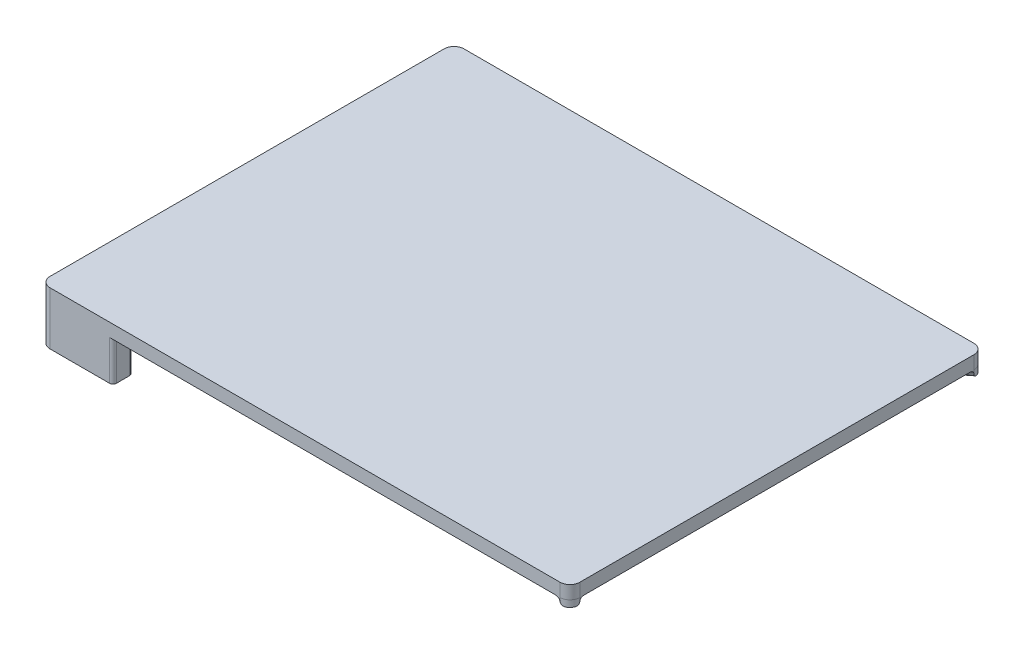
SolidWorks part; units mm, degrees
ref_plane "前视基准面" through (0, 0, 0) normal (0, 0, 1) x (1, 0, 0)
ref_plane "上视基准面" through (0, 0, 0) normal (0, 1, 0) x (1, 0, 0)
ref_plane "右视基准面" through (0, 0, 0) normal (1, 0, 0) x (0, 0, -1)
other "Configuration Table"
sketch "草图1" plane through (0, 0, 0) normal (0, 1, 0) x (1, 0, 0)
  line L1 (-42.7044, 26.7469) -> (117.2956, 26.7469)
  line L2 (-42.7044, 26.7469) -> (-42.7044, -98.2531)
  line L3 (-42.7044, -98.2531) -> (117.2956, -98.2531)
  line L4 (117.2956, 26.7469) -> (117.2956, -98.2531)
  dimension "D1" = 125
  dimension "D2" = 160
extrude "凸台-拉伸1" add sketch "草图1" along normal blind 4
sketch "草图4" plane through (0, 0, 0) normal (0, -1, 0) x (1, 0, 0)
  line L0 (-42.7044, 98.2531) -> (-20.7044, 98.2531)
  line L1 (-42.7044, 98.2531) -> (117.2956, 98.2531) construction
  line L2 (-20.7044, 98.2531) -> (-20.7044, 92.2531)
  line L6 (-36.7044, 76.2531) -> (-42.7044, 76.2531)
  line L7 (-42.7044, -26.7469) -> (-42.7044, 98.2531) construction
  line L8 (-42.7044, 76.2531) -> (-42.7044, 98.2531)
  line L11 (-36.7044, 76.2531) -> (-36.7044, 92.2531)
  line L12 (-36.7044, 92.2531) -> (-20.7044, 92.2531)
  dimension "D1" = 6
  dimension "D2" = 6
  dimension "D3" = 16
  dimension "D4" = 16
extrude "凸台-拉伸2" add sketch "草图4" along normal blind 12
fillet "圆角7" radius 1 1 edges at (-36.7044, -6, 76.2531)
fillet "圆角8" radius 1 1 edges at (-20.7044, -6, 92.2531)
fillet "圆角9" radius 3 1 edges at (-36.7044, -6, 92.2531)
fillet "圆角10" radius 1 1 edges at (-42.7044, -6, 76.2531)
fillet "圆角11" radius 1 1 edges at (-20.7044, -6, 98.2531)
fillet "圆角12" radius 3 1 edges at (-42.7044, -4, 98.2531)
fillet "圆角13" radius 3 3 edges at (117.2956, 2, 98.2531) (117.2956, 2, -26.7469) (-42.7044, 2, -26.7469)
sketch "草图5" plane through (0, 0, 0) normal (0, -1, 0) x (-1, 0, 0)
  line L0 (33.7044, -92.2531) -> (-117.2956, 23.7469) construction
  line L1 (-117.2956, 23.7469) -> (-114.2956, 26.7469) construction
  line L2 (-114.2956, 26.7469) -> (36.2671, -88.9172) construction
  line L3 (-117.2956, -95.2531) -> (39.7044, 26.7469) construction
  line L4 (39.7044, 26.7469) -> (42.7044, 23.7469) construction
  line L5 (42.7044, 23.7469) -> (-114.2956, -98.2531) construction
  line L6 (-114.2956, -98.2531) -> (-117.2956, -95.2531) construction
  line L7 (-36.837, -38.0623) -> (-114.2956, -98.2531)
  line L8 (-117.2956, -95.2531) -> (-40.287, -35.412)
  line L9 (-40.287, -35.412) -> (-117.2956, 23.7469)
  line L10 (-114.2956, 26.7469) -> (-36.837, -32.7577)
  line L11 (-36.837, -32.7577) -> (39.7044, 26.7469)
  line L12 (42.7044, 23.7469) -> (-33.4042, -35.3948)
  line L16 (33.7044, -92.2531) -> (36.7044, -89.2531)
  line L18 (-36.837, -38.0623) -> (32.7158, -91.4937)
  line L19 (32.7158, -91.4937) -> (35.2785, -88.1577)
  line L20 (35.2785, -88.1577) -> (-33.4042, -35.3948)
  arc A1 (42.7044, 23.7469) -> (39.7044, 26.7469) centre (39.7044, 23.7469) ccw construction
  arc A2 (-114.2956, 26.7469) -> (-117.2956, 23.7469) centre (-114.2956, 23.7469) ccw construction
  arc A3 (-117.2956, -95.2531) -> (-114.2956, -98.2531) centre (-114.2956, -95.2531) ccw construction
  spline S1 degree 2 poles (39.7044, 26.7469) (42.447, 26.4896) (42.7044, 23.7469) knots 0 0 0 1 1 1
  spline S2 degree 2 poles (-117.2956, 23.7469) (-117.0382, 26.4896) (-114.2956, 26.7469) knots 0 0 0 1 1 1
  spline S3 degree 2 poles (-114.2956, -98.2531) (-117.0382, -97.9957) (-117.2956, -95.2531) knots 0 0 0 1 1 1
extrude "凸台-拉伸10" add sketch "草图5" along normal blind 2 contours L19 L20 L12 S1 L11 L10 S2 L9 L8 S3 L7 L18
fillet "圆角14" radius 1 1 edges at (-0.9372, -2, 61.7763)
fillet "圆角15" radius 1 8 edges at (78.7913, 0, 65.3325) (78.7913, 0, 5.8325) (2.0606, 0, 64.778) (75.5663, 0, 68.1577) (-4.6501, 0, 5.8239) (-1.4337, 0, 3.0054) (75.5663, 0, 3.0054) (-0.9372, 0, 61.7763)
fillet "圆角16" radius 1 6 edges at (75.5663, -2, 3.0054) (-4.2421, -2, 6.141) (75.5663, -2, 68.1577) (78.7913, -2, 65.3325) (78.7913, -2, 5.8325) (2.0606, -2, 64.778)
sketch "草图6" plane through (0, 4, 0) normal (0, 1, 0) x (1, 0, 0)
  line L16 (100.6225, 11.8834) -> (110.6225, 11.8834)
  line L17 (110.6225, 6.8434) -> (100.6225, 6.8434)
  line L18 (65.6625, 11.8834) -> (75.6625, 11.8834)
  line L19 (75.6625, 6.8434) -> (65.6625, 6.8434)
  line L20 (100.6225, 9.3634) -> (75.6625, 9.3634) construction
  line L21 (112.6541, 26.7469) -> (-38.0751, 26.7469) construction
  line L22 (83.1425, -8.1366) -> (93.1425, -8.1366)
  line L23 (93.1425, -13.1766) -> (83.1425, -13.1766)
  line L24 (83.1425, 31.9034) -> (93.1425, 31.9034)
  line L25 (93.1425, 26.8634) -> (83.1425, 26.8634)
  line L26 (88.1425, -8.1366) -> (88.1425, 26.8634) construction
  line L27 (100.6225, -68.1966) -> (110.6225, -68.1966)
  line L28 (110.6225, -73.2366) -> (100.6225, -73.2366)
  line L29 (65.6625, -68.1966) -> (75.6625, -68.1966)
  line L30 (75.6625, -73.2366) -> (65.6625, -73.2366)
  line L31 (100.6225, -70.7166) -> (75.6625, -70.7166) construction
  line L32 (83.1425, -88.2166) -> (93.1425, -88.2166)
  line L33 (93.1425, -93.2566) -> (83.1425, -93.2566)
  line L34 (83.1425, -48.1766) -> (93.1425, -48.1766)
  line L35 (93.1425, -53.2166) -> (83.1425, -53.2166)
  line L36 (88.1425, -88.2166) -> (88.1425, -53.2166) construction
  line L37 (88.1425, -48.1766) -> (88.1425, -13.1766) construction
  line L38 (117.2956, -93.9867) -> (117.2956, 22.4859) construction
  line L43 (100.6225, -28.1566) -> (110.6225, -28.1566)
  line L48 (110.6225, -33.1966) -> (100.6225, -33.1966)
  line L49 (65.6625, -70.7166) -> (35.6625, -70.7166) construction
  line L50 (-21.7044, -98.2531) -> (112.6659, -98.2531) construction
  line L55 (110.6225, -68.1966) -> (110.6225, -33.1966) construction
  line L60 (65.6626, -28.1566) -> (75.6625, -28.1566)
  line L61 (33.6015, 9.3634) -> (65.6625, 9.3634) construction
  line L76 (75.6625, -33.1966) -> (65.6626, -33.1966)
  line L77 (58.1825, -90.7366) -> (83.1425, -90.7366) construction
  line L80 (100.6225, -30.6766) -> (75.6625, -30.6766) construction
  line L81 (27.9042, 12.255) -> (37.9042, 12.255)
  line L82 (37.9042, 7.215) -> (27.9042, 7.215)
  line L83 (45.4242, -7.765) -> (55.4242, -7.765)
  line L84 (55.4242, -12.805) -> (45.4242, -12.805)
  line L85 (45.4242, 32.275) -> (55.4242, 32.275)
  line L86 (55.4242, 27.235) -> (45.4242, 27.235)
  line L87 (50.4242, -7.765) -> (50.4242, 27.235) construction
  line L88 (27.9042, -67.825) -> (37.9042, -67.825)
  line L89 (37.9042, -72.865) -> (27.9042, -72.865)
  line L90 (45.4242, -88.2166) -> (55.4242, -88.2166)
  line L91 (55.4242, -93.2566) -> (45.4242, -93.2566)
  line L92 (45.4242, -47.805) -> (55.4242, -47.805)
  line L93 (55.4242, -52.845) -> (45.4242, -52.845)
  line L94 (50.4242, -88.2166) -> (50.4242, -52.845) construction
  line L95 (50.4242, -47.805) -> (50.4242, -12.805) construction
  line L96 (27.9443, -27.785) -> (37.9442, -27.785)
  line L97 (37.9442, -32.825) -> (27.9443, -32.825)
  line L98 (20.4642, -90.7366) -> (45.4242, -90.7366) construction
  line L105 (-7.2328, 12.2197) -> (2.7672, 12.2197)
  line L112 (2.7672, 7.1797) -> (-7.2328, 7.1797)
  line L113 (10.4642, -7.9446) -> (20.4642, -7.9446)
  line L116 (-30.7011, -90.69) -> (10.4642, -90.7366) construction
  line L117 (55.4242, -90.7366) -> (83.1425, -90.7366) construction
  line L118 (-24.4958, -7.3636) -> (-14.4958, -7.3636)
  line L119 (20.4642, -12.9846) -> (10.4642, -12.9846)
  line L120 (10.4642, 32.0954) -> (20.4642, 32.0954)
  line L121 (20.4642, 27.0554) -> (10.4642, 27.0554)
  line L122 (15.4642, -7.9446) -> (15.4642, 27.0554) construction
  line L123 (-7.2328, -68.0046) -> (2.7672, -68.0046)
  line L124 (2.7672, -73.0446) -> (-7.2328, -73.0446)
  line L125 (10.4642, -88.0246) -> (20.4642, -88.0246)
  line L126 (20.4642, -93.4485) -> (10.4642, -93.4485)
  line L127 (10.4642, -47.9846) -> (20.4642, -47.9846)
  line L128 (20.4642, -53.0246) -> (10.4642, -53.0246)
  line L129 (15.4642, -88.0246) -> (15.4642, -53.0246) construction
  line L130 (15.4642, -47.9846) -> (15.4642, -12.9846) construction
  line L131 (-7.1751, -28.8176) -> (2.8248, -28.8176)
  line L132 (2.8248, -33.8909) -> (-7.1751, -33.8909)
  line L133 (-22.5946, -90.7366) -> (10.4642, -90.7366) construction
  line L138 (-14.4958, -12.4036) -> (-24.4958, -12.4036)
  line L143 (-24.4958, -47.9846) -> (-14.4958, -47.9846)
  line L144 (-14.4958, -53.0246) -> (-24.4958, -53.0246)
  line L145 (-19.4958, -47.9846) -> (-19.4958, -12.4036) construction
  line L146 (10.4642, -50.5046) -> (-14.4958, -50.5046) construction
  line L147 (-42.7044, 22.4805) -> (-42.7044, -77.2531) construction
  line L148 (-23.4233, -86.8261) -> (-13.4233, -86.8261)
  line L149 (-13.4233, -91.8661) -> (-23.4233, -91.8661)
  line L150 (-41.9025, 12.2197) -> (-31.9025, 12.2197)
  line L151 (-31.9025, 7.1797) -> (-41.9025, 7.1797)
  line L152 (-42.1928, -68.0046) -> (-32.1928, -68.0046)
  line L153 (-32.1928, -73.0446) -> (-42.1928, -73.0446)
  line L154 (-42.1381, -28.8342) -> (-32.1382, -28.8342)
  line L155 (-32.1382, -33.8742) -> (-42.1381, -33.8742)
  line L156 (-7.2328, -70.5246) -> (-32.1928, -70.5246) construction
  line L157 (-7.1751, -31.3542) -> (-32.1382, -31.3542) construction
  line L158 (-7.2328, 9.6997) -> (-31.9025, 9.6997) construction
  arc A16 (110.6225, 11.8834) -> (110.6225, 6.8434) centre (110.6225, 9.3634) cw
  arc A17 (100.6225, 11.8834) -> (100.6225, 6.8434) centre (100.6225, 9.3634) ccw
  arc A18 (75.6625, 11.8834) -> (75.6625, 6.8434) centre (75.6625, 9.3634) cw
  arc A19 (65.6625, 11.8834) -> (65.6625, 6.8434) centre (65.6625, 9.3634) ccw
  arc A20 (93.1425, -8.1366) -> (93.1425, -13.1766) centre (93.1425, -10.6566) cw
  arc A21 (83.1425, -8.1366) -> (83.1425, -13.1766) centre (83.1425, -10.6566) ccw
  arc A22 (93.1425, 31.9034) -> (93.1425, 26.8634) centre (93.1425, 29.3834) cw
  arc A23 (83.1425, 31.9034) -> (83.1425, 26.8634) centre (83.1425, 29.3834) ccw
  arc A24 (110.6225, -68.1966) -> (110.6225, -73.2366) centre (110.6225, -70.7166) cw
  arc A25 (100.6225, -68.1966) -> (100.6225, -73.2366) centre (100.6225, -70.7166) ccw
  arc A26 (75.6625, -68.1966) -> (75.6625, -73.2366) centre (75.6625, -70.7166) cw
  arc A27 (65.6625, -68.1966) -> (65.6625, -73.2366) centre (65.6625, -70.7166) ccw
  arc A28 (93.1425, -88.2166) -> (93.1425, -93.2566) centre (93.1425, -90.7366) cw
  arc A29 (83.1425, -88.2166) -> (83.1425, -93.2566) centre (83.1425, -90.7366) ccw
  arc A30 (93.1425, -48.1766) -> (93.1425, -53.2166) centre (93.1425, -50.6966) cw
  arc A31 (83.1425, -48.1766) -> (83.1425, -53.2166) centre (83.1425, -50.6966) ccw
  arc A62 (110.6225, -28.1566) -> (110.6225, -33.1966) centre (110.6225, -30.6766) cw
  arc A63 (100.6225, -28.1566) -> (100.6225, -33.1966) centre (100.6225, -30.6766) ccw
  arc A64 (75.6625, -28.1566) -> (75.6625, -33.1966) centre (75.6625, -30.6766) cw
  arc A65 (65.6626, -28.1566) -> (65.6626, -33.1966) centre (65.6626, -30.6766) ccw
  arc A66 (37.9042, 12.255) -> (37.9042, 7.215) centre (37.9042, 9.735) cw
  arc A67 (27.9042, 12.255) -> (27.9042, 7.215) centre (27.9042, 9.735) ccw
  arc A68 (55.4242, -7.765) -> (55.4242, -12.805) centre (55.4242, -10.285) cw
  arc A69 (45.4242, -7.765) -> (45.4242, -12.805) centre (45.4242, -10.285) ccw
  arc A70 (55.4242, 32.275) -> (55.4242, 27.235) centre (55.4242, 29.755) cw
  arc A71 (45.4242, 32.275) -> (45.4242, 27.235) centre (45.4242, 29.755) ccw
  arc A72 (37.9042, -67.825) -> (37.9042, -72.865) centre (37.9042, -70.345) cw
  arc A73 (27.9042, -67.825) -> (27.9042, -72.865) centre (27.9042, -70.345) ccw
  arc A74 (55.4242, -88.2166) -> (55.4242, -93.2566) centre (55.4242, -90.7366) cw
  arc A75 (45.4242, -88.2166) -> (45.4242, -93.2566) centre (45.4242, -90.7366) ccw
  arc A76 (55.4242, -47.805) -> (55.4242, -52.845) centre (55.4242, -50.325) cw
  arc A77 (45.4242, -47.805) -> (45.4242, -52.845) centre (45.4242, -50.325) ccw
  arc A78 (37.9442, -27.785) -> (37.9442, -32.825) centre (37.9442, -30.305) cw
  arc A79 (27.9443, -27.785) -> (27.9443, -32.825) centre (27.9443, -30.305) ccw
  arc A94 (2.7672, 12.2197) -> (2.7672, 7.1797) centre (2.7672, 9.6997) cw
  arc A95 (-7.2328, 12.2197) -> (-7.2328, 7.1797) centre (-7.2328, 9.6997) ccw
  arc A96 (20.4642, -7.9446) -> (20.4642, -12.9846) centre (20.4642, -10.4646) cw
  arc A97 (10.4642, -7.9446) -> (10.4642, -12.9846) centre (10.4642, -10.4646) ccw
  arc A98 (20.4642, 32.0954) -> (20.4642, 27.0554) centre (20.4642, 29.5754) cw
  arc A99 (10.4642, 32.0954) -> (10.4642, 27.0554) centre (10.4642, 29.5754) ccw
  arc A100 (2.7672, -68.0046) -> (2.7672, -73.0446) centre (2.7672, -70.5246) cw
  arc A101 (-7.2328, -68.0046) -> (-7.2328, -73.0446) centre (-7.2328, -70.5246) ccw
  arc A102 (20.4642, -88.0246) -> (20.4642, -93.4485) centre (20.4642, -90.7366) cw
  arc A103 (10.4642, -88.0246) -> (10.4642, -93.4485) centre (10.4642, -90.7366) ccw
  arc A104 (20.4642, -47.9846) -> (20.4642, -53.0246) centre (20.4642, -50.5046) cw
  arc A105 (10.4642, -47.9846) -> (10.4642, -53.0246) centre (10.4642, -50.5046) ccw
  arc A106 (2.8248, -28.8176) -> (2.8248, -33.8909) centre (2.8248, -31.3542) cw
  arc A107 (-7.1751, -28.8176) -> (-7.1751, -33.8909) centre (-7.1751, -31.3542) ccw
  arc A116 (-14.4958, -7.3636) -> (-14.4958, -12.4036) centre (-14.4958, -9.8836) cw
  arc A117 (-24.4958, -7.3636) -> (-24.4958, -12.4036) centre (-24.4958, -9.8836) ccw
  arc A118 (-14.4958, -47.9846) -> (-14.4958, -53.0246) centre (-14.4958, -50.5046) cw
  arc A119 (-24.4958, -47.9846) -> (-24.4958, -53.0246) centre (-24.4958, -50.5046) ccw
  arc A120 (-13.4233, -86.8261) -> (-13.4233, -91.8661) centre (-13.4233, -89.3461) cw
  arc A121 (-23.4233, -86.8261) -> (-23.4233, -91.8661) centre (-23.4233, -89.3461) ccw
  arc A122 (-31.9025, 12.2197) -> (-31.9025, 7.1797) centre (-31.9025, 9.6997) cw
  arc A123 (-41.9025, 12.2197) -> (-41.9025, 7.1797) centre (-41.9025, 9.6997) ccw
  arc A124 (-32.1928, -68.0046) -> (-32.1928, -73.0446) centre (-32.1928, -70.5246) cw
  arc A125 (-42.1928, -68.0046) -> (-42.1928, -73.0446) centre (-42.1928, -70.5246) ccw
  arc A126 (-32.1382, -28.8342) -> (-32.1382, -33.8742) centre (-32.1382, -31.3542) cw
  arc A127 (-42.1381, -28.8342) -> (-42.1381, -33.8742) centre (-42.1381, -31.3542) ccw
  point P28 (88.1425, 9.3634)
  point P29 (88.1425, 9.3634)
  point P56 (88.1425, -70.7166)
  point P57 (88.1425, -70.7166)
  dimension "D1" = 10
  dimension "D2" = 2.52
  dimension "D3" = 10
  dimension "D4" = 10
  dimension "D5" = 2.52
  dimension "D6" = 10
  dimension "D7" = 24.96
  dimension "D8" = 10
  dimension "D9" = 2.52
  dimension "D10" = 10
  dimension "D11" = 10
  dimension "D12" = 2.52
  dimension "D13" = 10
  dimension "D14" = 35
  dimension "D15" = 10
  dimension "D16" = 2.52
  dimension "D17" = 10
  dimension "D18" = 10
  dimension "D19" = 2.52
  dimension "D20" = 10
  dimension "D21" = 24.96
  dimension "D22" = 10
  dimension "D23" = 2.52
  dimension "D24" = 10
  dimension "D25" = 10
  dimension "D26" = 2.52
  dimension "D27" = 10
  dimension "D28" = 35
  dimension "D29" = 35
  dimension "D30" = 35
  dimension "D31" = 24.96
  dimension "D32" = 10
  dimension "D33" = 2.52
  dimension "D34" = 10
  dimension "D35" = 10
  dimension "D36" = 10
  dimension "D37" = 10
  dimension "D38" = 10
  dimension "D39" = 10
  dimension "D40" = 2.52
  dimension "D41" = 10
  dimension "D42" = 10
  dimension "D43" = 10
  dimension "D44" = 10
  dimension "D45" = 10
  dimension "D46" = 35
  dimension "D47" = 10
  dimension "D48" = 2.52
  dimension "D49" = 10
  dimension "D50" = 10
  dimension "D51" = 10
  dimension "D52" = 10
  dimension "D53" = 10
  dimension "D54" = 10
  dimension "D55" = 2.52
  dimension "D56" = 10
  dimension "D57" = 10
  dimension "D58" = 10
  dimension "D59" = 10
  dimension "D60" = 10
  dimension "D61" = 35
  dimension "D62" = 24.96
  dimension "D63" = 24.96
  dimension "D64" = 10
  dimension "D65" = 10
  dimension "D66" = 24.96
  dimension "D67" = 10
  dimension "D68" = 10
  dimension "D69" = 10
  dimension "D70" = 24.96
